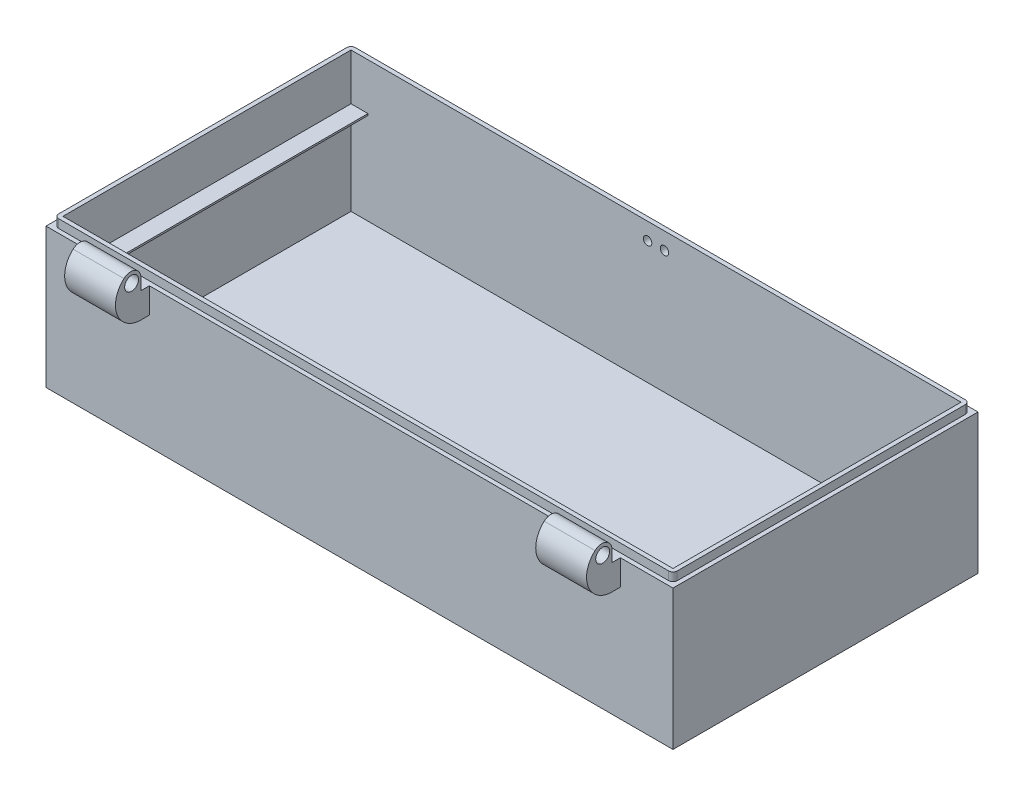
SolidWorks part; units mm, degrees
ref_plane "Front Plane" through (0, 0, 0) normal (0, 0, 1) x (1, 0, 0)
ref_plane "Top Plane" through (0, 0, 0) normal (0, 1, 0) x (1, 0, 0)
ref_plane "Right Plane" through (0, 0, 0) normal (1, 0, 0) x (0, 0, -1)
sketch "Sketch2" plane through (0, 0, 0) normal (0, 0, 1) x (1, 0, 0)
  line L0 (-185, 0) -> (185, 0)
  line L1 (185, 0) -> (185, 82.5)
  line L2 (185, 82.5) -> (182.5, 82.5)
  line L3 (182.5, 82.5) -> (182.5, 87.5)
  line L4 (0, 1.3085) -> (0, -0.7826) construction
  line L5 (182.5, 87.5) -> (180, 87.5)
  line L8 (180, 80.5) -> (180, 5)
  line L9 (180, 5) -> (-180, 5)
  line L10 (-180, 80.5) -> (-180, 5)
  line L13 (-182.5, 87.5) -> (-180, 87.5)
  line L14 (-182.5, 82.5) -> (-182.5, 87.5)
  line L15 (-185, 82.5) -> (-182.5, 82.5)
  line L16 (-185, 0) -> (-185, 82.5)
  line L17 (180, 87.5) -> (180, 80.5)
  line L18 (-180, 87.5) -> (-180, 80.5)
  point P14 (0, 5)
  point P21 (0, 0)
  dimension "D1" = 185
  dimension "D2" = 87.5
  dimension "D3" = 2.5
  dimension "D4" = 5
  dimension "D5" = 5
  dimension "D6" = 5
  dimension "D7" = 75.5
extrude "Boss-Extrude1" add sketch "Sketch2" along normal mid plane 170
sketch "Sketch3" plane through (0, 0, 0) normal (0, 1, 0) x (1, 0, 0)
  line L0 (-185, -85) -> (-185, -90)
  line L1 (-185, -90) -> (185, -90)
  line L2 (185, -90) -> (185, -85)
  line L3 (-53.5244, 0) -> (68.263, 0) construction
  line L4 (-185, -85) -> (185, -85)
  line L5 (-185, 85) -> (-185, 90)
  line L6 (185, 90) -> (185, 85)
  line L7 (-185, 85) -> (185, 85)
  line L8 (-185, 90) -> (185, 90)
  dimension "D1" = 5
extrude "Boss-Extrude2" add sketch "Sketch3" along normal blind 87.5
sketch "Sketch4" plane through (185, 0, 0) normal (1, 0, 0) x (0, 0, -1)
  line L0 (-90, 87.5) -> (-87.5, 87.5)
  line L1 (-90, 87.5) -> (-85, 87.5) construction
  line L2 (-87.5, 87.5) -> (-87.5, 82.5)
  line L3 (-87.5, 82.5) -> (-90, 82.5)
  line L4 (-90, 87.5) -> (-90, 0) construction
  line L5 (-90, 82.5) -> (-90, 87.5)
  line L8 (0, 18.8036) -> (0, -11.4284) construction
  line L9 (90, 87.5) -> (87.5, 87.5)
  line L10 (90, 82.5) -> (90, 87.5)
  line L11 (87.5, 82.5) -> (90, 82.5)
  line L12 (87.5, 87.5) -> (87.5, 82.5)
  dimension "D1" = 5
extrude "Cut-Extrude1" cut sketch "Sketch4" against normal through all
sketch "Sketch5" plane through (0, 0, -87.5) normal (0, 0, -1) x (-1, 0, 0)
  line L0 (-185, 87.5) -> (-182.5, 87.5)
  line L1 (185, 87.5) -> (-185, 87.5) construction
  line L2 (-182.5, 87.5) -> (-182.5, 82.5)
  line L3 (185, 82.5) -> (-185, 82.5) construction
  line L4 (-182.5, 82.5) -> (-185, 82.5)
  line L5 (-185, 82.5) -> (-185, 87.5)
  line L6 (0, 47.5482) -> (0, -36.4606) construction
  line L7 (185, 82.5) -> (185, 87.5)
  line L8 (182.5, 82.5) -> (185, 82.5)
  line L9 (182.5, 87.5) -> (182.5, 82.5)
  line L10 (185, 87.5) -> (182.5, 87.5)
  dimension "D1" = 2.5
extrude "Cut-Extrude2" cut sketch "Sketch5" against normal through all and the other way through all
fillet "Fillet1" radius 2.5 4 edges at (-182.5, 85, -87.5) (-182.5, 85, 87.5) (182.5, 85, 87.5) (182.5, 85, -87.5)
ref_plane "Plane14" through (0, 60, 0) normal (0, 1, 0) x (1, 0, 0)
sketch "Sketch6" plane through (0, 60, 0) normal (0, 1, 0) x (1, 0, 0)
  line L0 (-180, -85) -> (-170, -85)
  line L1 (180, -85) -> (-180, -85) construction
  line L2 (-170, -85) -> (-170, 85)
  line L3 (180, 85) -> (-180, 85) construction
  line L4 (-170, 85) -> (-180, 85)
  line L5 (-180, 85) -> (-180, -85)
  line L6 (0, -57.2438) -> (0, 45.3734) construction
  line L7 (170, 85) -> (180, 85)
  line L8 (170, -85) -> (170, 85)
  line L9 (180, -85) -> (170, -85)
  line L10 (180, 85) -> (180, -85)
  dimension "D1" = 10
extrude "Boss-Extrude3" add sketch "Sketch6" against normal blind 10
fillet "Fillet2" radius 9 2 edges at (170, 50, 0) (-170, 50, 0) profile chamfer
fillet "Fillet3" [suppressed] radius 5
sketch "Sketch7" [suppressed] plane through (0, 0, 0) normal (0, -1, 0) x (-1, 0, 0)
  line L0 (0, -10.1292) -> (0, 15.0585) construction
  line L1 (13.1665, 0) -> (-15.6944, 0) construction
  line L2 (177.7348, -70) -> (149.8539, -70) construction
  line L3 (176.944, 70) -> (151.0402, 70) construction
  line L4 (-150.8633, 70) -> (-177.9968, 70) construction
  line L5 (-152.1641, -70) -> (-177.2854, -70) construction
  circle A0 centre (165, -70) radius 10
  circle A1 centre (-165, -70) radius 10
  circle A2 centre (-165, 70) radius 10
  circle A3 centre (165, 70) radius 10
  dimension "D1" = 20
  dimension "D2" = 165
  dimension "D3" = 70
extrude "Boss-Extrude4" [suppressed] add sketch "Sketch7" along normal blind 5
fillet "Fillet4" [suppressed] radius 5
fillet "Fillet5" [suppressed] radius 2
sketch "Sketch11" plane through (0, 82.5, 0) normal (0, 1, 0) x (1, 0, 0)
  line L0 (184.7021, -95) -> (-189.7557, -95)
  line L1 (-185, -90) -> (185, -90) construction
  dimension "D1" = 5
sketch "Sketch8" plane through (0, 82.5, 0) normal (0, 1, 0) x (1, 0, 0)
  line L0 (-154, -95) -> (-154, -110)
  line L1 (-154, -110) -> (-124, -110)
  line L2 (-124, -110) -> (-124, -95)
  line L3 (-185, -90) -> (185, -90) construction
  line L4 (-124, -95) -> (-154, -95)
  line L5 (-185, -90) -> (-185, 90) construction
  dimension "D1" = 30
  dimension "D2" = 15
  dimension "D3" = 5
  dimension "D4" = 31
revolve "Revolve1" add sketch "Sketch8" angle 180 mid plane about L0
sketch "Sketch9" plane through (-154, 0, 0) normal (-1, 0, 0) x (0, 0, 1)
  circle A0 centre (100.5, 89) radius 4.1
  arc A1 (95, 67.5) -> (95, 97.5) centre (95, 82.5) ccw construction
  point P7 (110, 82.5)
  dimension "D1" = 8.2
  dimension "D2" = 8.5
  dimension "D3" = 9.5
fillet "Fillet9" radius 6 1 edges at (-139, 97.5, 95)
sketch "Sketch12" plane through (-154, 0, 0) normal (-1, 0, 0) x (0, 0, 1)
  line L0 (95, 82.5) -> (90, 82.5)
  line L1 (95, 89.2082) -> (95, 67.5) construction
  line L2 (90, 82.5) -> (90, 67.5)
  line L3 (90, 82.5) -> (90, 0) construction
  line L4 (90, 67.5) -> (95, 67.5)
  line L5 (95, 67.5) -> (95, 82.5)
extrude "Boss-Extrude5" add sketch "Sketch12" against normal blind 30
mirror "Mirror4" about plane through (0, 0, 0) normal (1, 0, 0) of "Revolve1", "Boss-Extrude5"
mirror "Mirror5" about plane through (0, 0, 0) normal (1, 0, 0) of "Revolve1"
extrude "Cut-Extrude4" cut sketch "Sketch9" against normal through all
fillet "Fillet11" radius 6 1 edges at (139, 97.5, 95)
sketch "Sketch13" plane through (0, 0, -90) normal (0, 0, -1) x (-1, 0, 0)
  line L0 (0, 19.8668) -> (0, -13.2023) construction
  line L1 (180, 87.5) -> (-180, 87.5) construction
  circle A0 centre (-5, 77.5) radius 2.5
  circle A1 centre (5, 77.5) radius 2.5
  dimension "D1" = 5
  dimension "D2" = 5
  dimension "D3" = 10
extrude "Cut-Extrude5" cut sketch "Sketch13" against normal blind 30
